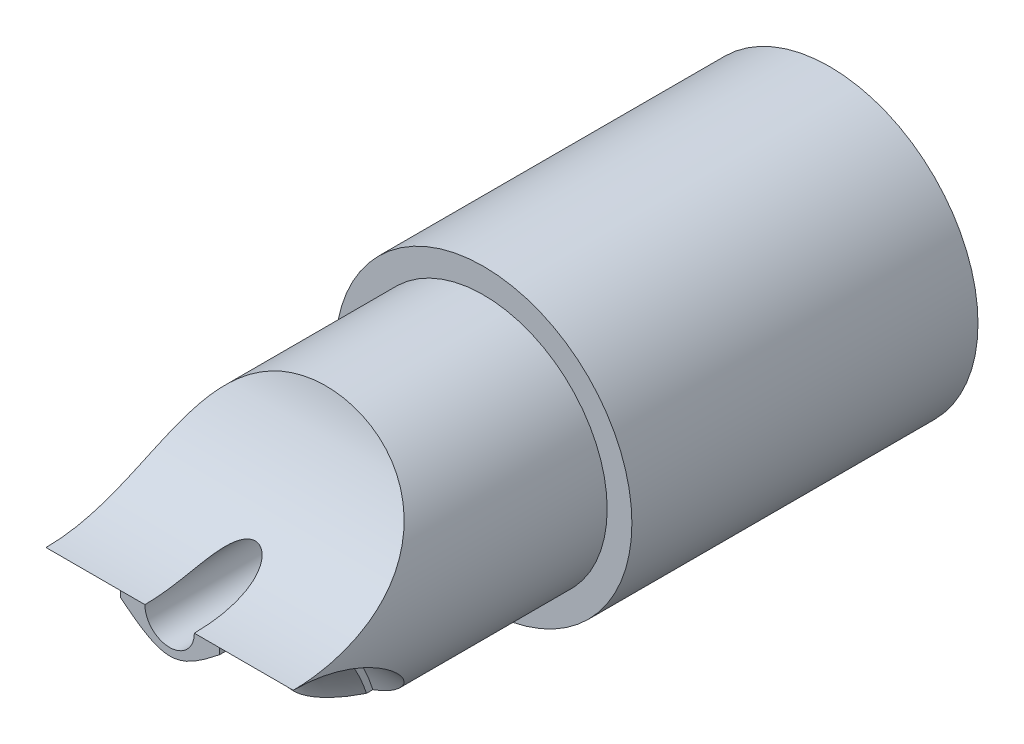
SolidWorks part; units mm, degrees
ref_plane "Front" through (0, 0, 0) normal (0, 0, 1) x (1, 0, 0)
ref_plane "Top" through (0, 0, 0) normal (0, 1, 0) x (1, 0, 0)
ref_plane "Right" through (0, 0, 0) normal (1, 0, 0) x (0, 0, -1)
sketch "Base sketch" plane through (0, 0, 0) normal (0, 0, 1) x (1, 0, 0)
  circle A0 centre (0, 0) radius 6
  dimension "D1" = 12
extrude "Boss-Extrude1" add sketch "Base sketch" along normal blind 14
sketch "Sketch2" plane through (0, 0, 14) normal (0, 0, 1) x (1, 0, 0)
  circle A0 centre (0, 0) radius 5
  dimension "D1" = 10
extrude "Boss-Extrude2" add sketch "Sketch2" along normal blind 12.7
sketch "Sketch3" plane through (0, 0, 26.7) normal (0, 0, 1) x (1, 0, 0)
  circle A0 centre (0, 0) radius 1
  dimension "D1" = 2
extrude "Cut-Extrude1" cut sketch "Sketch3" against normal through all
sketch "Sketch4" plane through (0, 0, 0) normal (0, 0, -1) x (-1, 0, 0)
  circle A0 centre (0, 0) radius 2.25
  dimension "D1" = 4.5
extrude "Cut-Extrude2" cut sketch "Sketch4" against normal blind 6.25
sketch "Sketch5" plane through (0, 0, 0) normal (1, 0, 0) x (0, 0, -1)
  line L0 (-26.7, 6.5) -> (-26.7, -6.5) construction
  line L4 (-26.7, 1) -> (-26.7, -1) construction
  circle A0 centre (-26.7, 6.5) radius 6.5
  circle A1 centre (-26.7, -6.5) radius 6.5
  point P2 (-26.7, 0)
  dimension "D1" = 13
extrude "Cut-Extrude3" cut sketch "Sketch5" against normal through all and the other way through all contours A0 region at (0, 6.5, 26.7)
ref_plane "Plane1" through (0.0147, 0, 0) normal (1, 0, 0) x (0, 0, -1)
ref_plane "Plane2" through (2.0147, 0, 0) normal (1, 0, 0) x (0, 0, -1)
ref_plane "Plane3" through (-1.9853, 0, 0) normal (1, 0, 0) x (0, 0, -1)
sketch "Sketch6" plane through (0.0147, 0, 0) normal (1, 0, 0) x (0, 0, -1)
  circle A0 centre (-26.7, -6.5) radius 5.2
  circle A1 centre (-26.7, -6.5) radius 6.5
  circle A2 centre (-26.7, -6.5) radius 6.5
  dimension "D1" = 0
sketch "Sketch7" plane through (2.0147, 0, 0) normal (1, 0, 0) x (0, 0, -1)
  circle A1 centre (-26.7, -6.5) radius 6.25
  circle A2 centre (-26.7, -6.5) radius 6.5
sketch "Sketch8" plane through (-1.9853, 0, 0) normal (1, 0, 0) x (0, 0, -1)
  circle A1 centre (-26.7, -6.5) radius 6.25
  circle A2 centre (-26.7, -6.5) radius 6.5
loft "Loft1" add section "Sketch8" section "Sketch6" section "Sketch7" connector at (-1.9853, -12.75, 26.7) connector at (0.0147, -11.7, 26.7) connector at (2.0147, -12.75, 26.7)
combine bodies "Combine3" operation type subtract main body 105 bodies to subtract 106
extrude "Cut-Extrude5" cut sketch "Sketch8<4>" against normal blind 10 contours A2
sketch "Sketch8<4>" plane through (-1.9853, 0, 0) normal (1, 0, 0) x (0, 0, -1) same geometry as "Sketch8"
extrude "Cut-Extrude6" cut sketch "Sketch7<5>" along normal blind 10 contours A2
sketch "Sketch7<5>" plane through (2.0147, 0, 0) normal (1, 0, 0) x (0, 0, -1) same geometry as "Sketch7"
chamfer "Chamfer1" distance 1.25 angle 45 1 edges at (-2.25, 0, 6.25)
sketch "Sketch9" plane through (0, 0, 26.7) normal (0, 0, 1) x (1, 0, 0)
  line L1 (-6.4139, 2.5286) -> (6.6023, 2.5286)
  line L2 (-6.4139, 2.5286) -> (-6.4139, -3.1698)
  line L3 (-6.4139, -3.1698) -> (6.6023, -3.1698)
  line L4 (6.6023, 2.5286) -> (6.6023, -3.1698)
